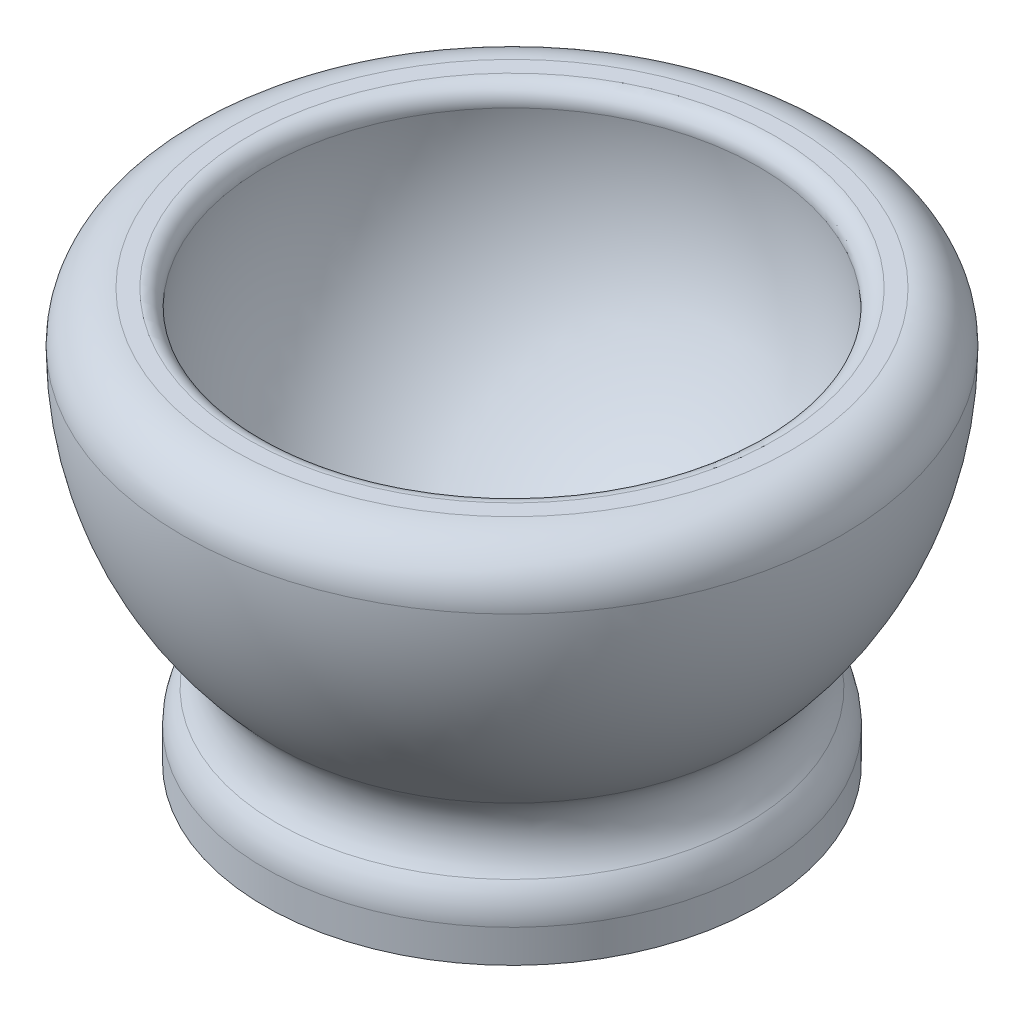
SolidWorks part; units mm, degrees
ref_plane "前视基准面" through (0, 0, 0) normal (0, 0, 1) x (1, 0, 0)
ref_plane "上视基准面" through (0, 0, 0) normal (0, 1, 0) x (1, 0, 0)
ref_plane "右视基准面" through (0, 0, 0) normal (1, 0, 0) x (0, 0, -1)
other "Configuration Table"
sketch "草图1" plane through (0, 0, 0) normal (0, 1, 0) x (1, 0, 0)
  line L0 (-24.0835, 0) -> (25.1351, 0) construction
  line L1 (-15.1, 0) -> (-20, 0)
  line L2 (20, 0) -> (15.1, 0)
  arc A0 (-20, 0) -> (20, 0) centre (0, 0) ccw
  arc A1 (-15.1, 0) -> (15.1, 0) centre (0, 0) ccw
  circle A3 centre (0, 0) radius 20 construction
  circle A4 centre (0, 0) radius 15.1 construction
  point P1 (15, 0)
  point P7 (19.1261, 5.8474)
  dimension "D1" = 40
  dimension "D2" = 4.9
revolve "旋转5" add sketch "草图1" angle 360 about L0
sketch "草图2" plane through (0, 0, 0) normal (1, 0, 0) x (0, 0, -1)
  line L1 (-37.1806, 35) -> (36.2954, 35)
  line L2 (-37.1806, 35) -> (-37.1806, 3)
  line L3 (-37.1806, 3) -> (36.2954, 3)
  line L4 (36.2954, 35) -> (36.2954, 3)
  dimension "D1" = 35
  dimension "D2" = 3
extrude "切除-拉伸1" cut sketch "草图2" against normal through all and the other way through all
fillet "圆角1" radius 1 1 edges at (0, 3, -14.799)
ref_plane "基准面1" through (0, -22, 0) normal (0, 1, 0) x (1, 0, 0)
sketch "草图3" plane through (0, -22, 0) normal (0, 1, 0) x (1, 0, 0)
  circle A0 centre (0, 0) radius 6
  dimension "D1" = 12
extrude "凸台-拉伸1" add sketch "草图3" along normal up to next
sketch "草图4" plane through (0, -22, 0) normal (0, -1, 0) x (-1, 0, 0)
  circle A0 centre (0, 0) radius 15
  dimension "D1" = 30
extrude "凸台-拉伸2" add sketch "草图4" against normal blind 5
fillet "圆角3" radius 3 1 edges at (0, 3, -19.7737)
fillet "圆角4" radius 3 1 edges at (0, -17, -15)
fillet "圆角5" radius 3 1 edges at (0, -17, -10.5357)
